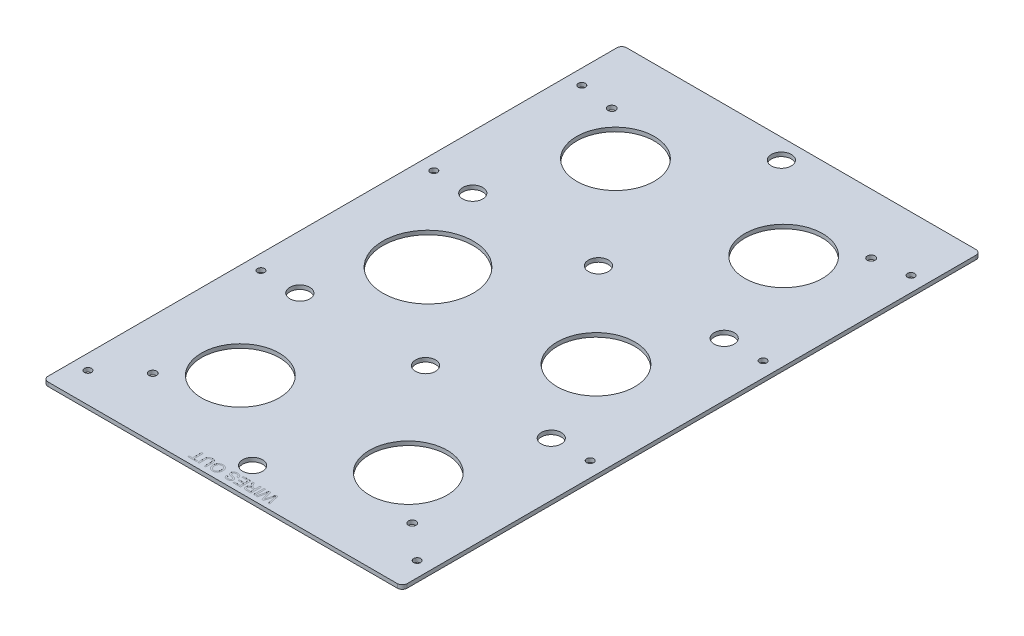
SolidWorks part; units mm, degrees
ref_plane "Front" through (0, 0, 0) normal (0, 0, 1) x (1, 0, 0)
ref_plane "Top" through (0, 0, 0) normal (0, 1, 0) x (1, 0, 0)
ref_plane "Right" through (0, 0, 0) normal (1, 0, 0) x (0, 0, -1)
sketch "Sketch1" plane through (0, 0, 0) normal (0, 1, 0) x (1, 0, 0)
  line L0 (455.7433, -88.0689) -> (455.6163, -88.0689) construction
  line L1 (422.7361, 215.4611) -> (644.9861, 215.4611)
  line L2 (419.5611, 212.2861) -> (419.5611, -149.6639)
  line L3 (422.7361, -152.8389) -> (644.9861, -152.8389)
  line L4 (648.1611, 212.2861) -> (648.1611, -149.6639)
  line L5 (419.5611, 215.4611) -> (648.1611, -152.8389) construction
  line L6 (419.5611, -152.8389) -> (648.1611, 215.4611) construction
  line L7 (460.7474, 51.3754) -> (499.9392, 11.3754) construction
  line L8 (560.8486, -152.8389) -> (644.9861, -152.8389) construction
  line L9 (648.1611, -149.6639) -> (648.1611, 212.2861) construction
  circle A0 centre (587.3789, -88.1975) radius 24.727
  circle A1 centre (587.3789, 31.2468) radius 24.727
  circle A2 centre (480.3433, -88.0689) radius 24.727
  circle A4 centre (480.3433, 150.6911) radius 24.727
  circle A5 centre (587.3789, 150.6911) radius 24.727
  arc A6 (485.3001, -112.1644) -> (482.9516, -63.6076) centre (480.3433, -88.0689) ccw construction
  arc A7 (485.3001, -112.1644) -> (475.3865, -63.9735) centre (480.3433, -88.0689) ccw construction
  arc A8 (648.1611, 212.2861) -> (644.9861, 215.4611) centre (644.9861, 212.2861) ccw
  arc A9 (419.5611, 212.2861) -> (422.7361, 215.4611) centre (422.7361, 212.2861) cw
  arc A10 (419.5611, -149.6639) -> (422.7361, -152.8389) centre (422.7361, -149.6639) ccw
  arc A11 (644.9861, -152.8389) -> (648.1611, -149.6639) centre (644.9861, -149.6639) ccw
  circle A12 centre (480.3433, 31.3754) radius 28.7693
  circle A13 centre (453.8511, -23.718) radius 2.2479 construction
  circle A14 centre (453.8511, -23.718) radius 2.2479 construction
  circle A15 centre (533.8611, -23.7222) radius 2.2479 construction
  circle A16 centre (533.8611, -23.7222) radius 2.2479 construction
  circle A17 centre (613.8711, -23.718) radius 2.2479 construction
  circle A18 centre (613.8711, -23.718) radius 2.2479 construction
  circle A19 centre (613.8711, 86.3402) radius 2.2479 construction
  circle A20 centre (613.8711, 86.3402) radius 2.2479 construction
  circle A21 centre (533.8611, 86.3444) radius 2.2479 construction
  circle A22 centre (533.8611, 86.3444) radius 2.2479 construction
  circle A23 centre (453.8511, 86.3402) radius 2.2479 construction
  circle A24 centre (453.8511, 86.3402) radius 2.2479 construction
  circle A25 centre (533.8611, 202.7611) radius 2.2479 construction
  circle A26 centre (533.8611, 202.7611) radius 2.2479 construction
  circle A27 centre (533.8611, -133.7889) radius 2.2479 construction
  circle A28 centre (533.8611, -133.7889) radius 2.2479 construction
  circle A29 centre (533.8611, -133.7889) radius 6.35
  circle A30 centre (613.8711, -23.718) radius 6.35
  circle A31 centre (533.8611, -23.7222) radius 6.35
  circle A32 centre (453.8511, -23.718) radius 6.35
  circle A33 centre (613.8711, 86.3402) radius 6.35
  circle A34 centre (533.8611, 86.3444) radius 6.35
  circle A35 centre (453.8511, 86.3402) radius 6.35
  circle A36 centre (533.8611, 202.7611) radius 6.35
  circle A37 centre (616.4111, 177.3611) radius 2.4574 construction
  circle A38 centre (616.4111, 177.3611) radius 2.4575
  circle A39 centre (451.3111, 177.3611) radius 2.4574 construction
  circle A40 centre (451.3111, 177.3611) radius 2.4575
  circle A41 centre (451.3111, -114.7389) radius 2.4575 construction
  circle A42 centre (451.3111, -114.7389) radius 2.4575
  circle A43 centre (616.4111, -114.7389) radius 2.4575 construction
  circle A44 centre (616.4111, -114.7389) radius 2.4575
  circle A45 centre (429.0861, 180.5361) radius 2.2479 construction
  circle A46 centre (429.0861, 180.5361) radius 2.2479
  circle A47 centre (429.0861, 86.3444) radius 2.2479 construction
  circle A48 centre (429.0861, 86.3444) radius 2.2479
  circle A49 centre (638.6361, 180.5361) radius 2.2479 construction
  circle A50 centre (638.6361, 180.5361) radius 2.2479
  circle A51 centre (638.6361, 86.3444) radius 2.2479 construction
  circle A52 centre (638.6361, 86.3444) radius 2.2479
  circle A53 centre (638.6361, -23.7222) radius 2.2479 construction
  circle A54 centre (638.6361, -23.7222) radius 2.2479
  circle A55 centre (429.0861, -23.7222) radius 2.2479 construction
  circle A56 centre (429.0861, -23.7222) radius 2.2479
  circle A57 centre (429.0861, -133.7889) radius 2.2479 construction
  circle A58 centre (429.0861, -133.7889) radius 2.2479
  circle A59 centre (638.6361, -133.7889) radius 2.2479 construction
  circle A60 centre (638.6361, -133.7889) radius 2.2479
  point P0 (533.8611, 31.3111)
  dimension "D3" = 0.127
  dimension "D4" = 3.175
  dimension "D5" = 12.7
  dimension "D1" = 228.6
  dimension "D2" = 368.3
extrude "Boss-Extrude1" add sketch "Sketch1" along normal blind 2.54
sketch "Sketch2" plane through (0, 2.54, 0) normal (0, 1, 0) x (1, 0, 0)
  line L0 (560.6537, -142.8389) -> (560.6537, -152.8389) construction
  line L2 (560.6537, -142.8389) -> (509.8537, -142.8389) construction
  line L3 (422.7361, -152.8389) -> (644.9861, -152.8389) construction
  line L4 (648.1611, -149.6639) -> (648.1611, 212.2861) construction
  text T0 "WIRES OUT" font "Arial" height in points 26
  dimension "D1" = 10
  dimension "D2" = 50.8
  dimension "D3" = 87.5074
extrude "Cut-Extrude2" cut sketch "Sketch2" against normal blind 0.0254
